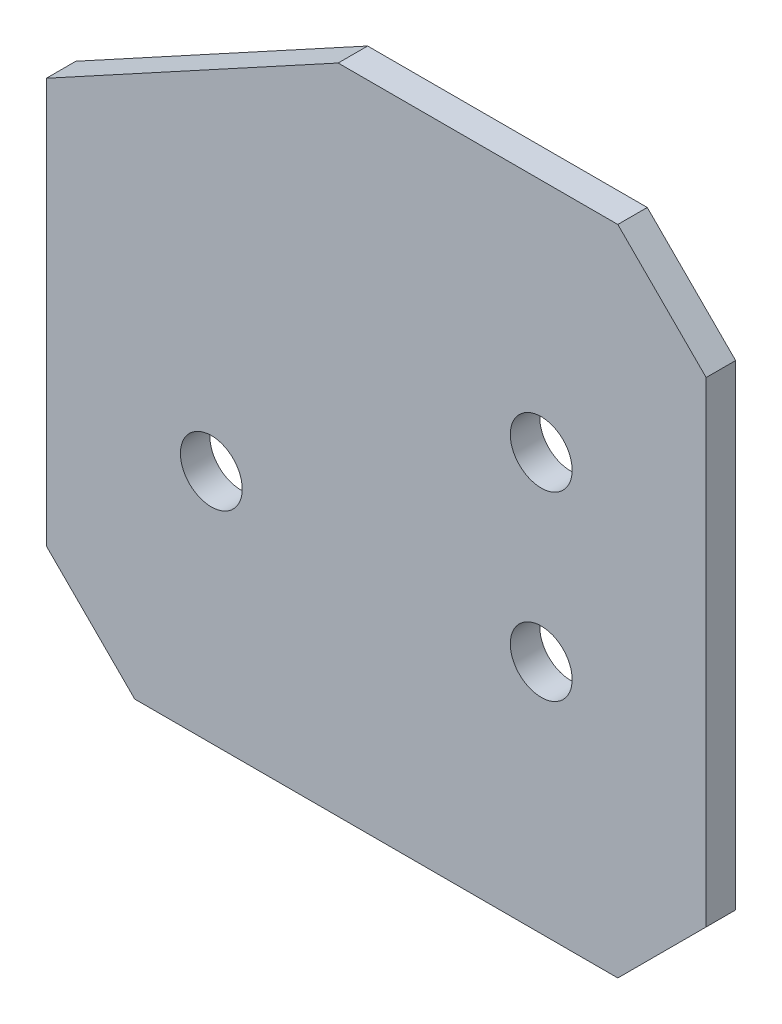
SolidWorks part; units mm, degrees
note: The reader was unsure of these and kept them because the rebuilt part matched: thickness of "Базовая кромка1", "Листовой металл3", "Листовой металл4".
material "AISI 1020"
ref_plane "Спереди" through (0, 0, 0) normal (0, 0, 1) x (1, 0, 0)
ref_plane "Сверху" through (0, 0, 0) normal (0, 1, 0) x (1, 0, 0)
ref_plane "Справа" through (0, 0, 0) normal (1, 0, 0) x (0, 0, -1)
sketch "Эскиз1" plane through (0, 0, 0) normal (0, 0, 1) x (1, 0, 0)
  line L0 (0, -1000) -> (0, 49000) construction
  line L1 (56, 3) -> (-56, 3)
  line L2 (-530.3264, 86.7738) -> (144.1634, 86.7738) construction
  line L3 (-56, 3) -> (-56, 113.7738)
  line L5 (-537.2086, 113.7738) -> (144.1634, 113.7738) construction
  line L6 (-56, 113.7738) -> (56, 113.7738)
  line L7 (133.9446, 3) -> (-133.9446, 3) construction
  line L8 (133.9446, 3) -> (-133.9446, 3) construction
  line L9 (-15, 30) -> (-15, 86.7738) construction
  line L10 (164.1634, 30) -> (-740.8168, 30) construction
  line L11 (0, 73.7738) -> (-56, 73.7738) construction
  line L12 (56, 3) -> (56, 113.7738)
  circle A0 centre (-28, 73.7738) radius 5.25 construction
  circle A1 centre (-28, 73.7738) radius 13 construction
  circle A2 centre (-28, 43) radius 5.25
  circle A3 centre (-28, 43) radius 13 construction
  circle A4 centre (28, 73.7738) radius 5.25
  circle A5 centre (28, 43) radius 5.25
  point P27 (-28, 73.7738)
  point P33 (0, 3)
  point P34 (0, 113.7738)
  dimension "D1" = 10.5
  dimension "D2" = 26
base flange "Базовая кромка1" sketch "Эскиз1" thickness 5 reverse thickness direction no parameters "D1"=0.74
chamfer "Фаска1" distance 15 angle 45 4 edges at (56, 3, -2.5) (-56, 3, -2.5) (56, 113.7738, -2.5) (-56, 113.7738, -2.5)
sketch "Эскиз2" plane through (0, 0, 0) normal (0, 0, 1) x (1, 0, 0)
  line L0 (-56, 113.7738) -> (-56, 86.7684)
  line L1 (-56, 3) -> (-56, 113.7738) construction
  line L2 (-56, 86.7684) -> (-6.4685, 113.7738)
  line L3 (-56, 113.7738) -> (56, 113.7738) construction
  line L4 (-6.4685, 113.7738) -> (-56, 113.7738)
  line L5 (-6.4685, 113.7738) -> (-160.121, 30) construction
extrude "Вырез-Вытянуть1" cut sketch "Эскиз2" against normal blind 10
sketch "Сгиб-Линии1" [suppressed] plane through (0, 0, 0) normal (0, 1, 0) x (1, 0, 0)
sketch "Граничная рамка1" [suppressed] plane through (0, 0, 0) normal (0, 1, 0) x (1, 0, 0)
sheet metal parameters "Листовой металл3" thickness 5 parameters "D1"=0.74, "D7"=4
flat pattern "Развертка3" [suppressed]
sketch "Сгиб-Линии2" plane through (0, 0, 0) normal (0, 1, 0) x (1, 0, 0)
sketch "Граничная рамка2" [suppressed] plane through (0, 0, 0) normal (0, 1, 0) x (1, 0, 0)
sheet metal parameters "Листовой металл4" thickness 5 parameters "D1"=0.74, "D7"=4
flat pattern "Развертка3"
sketch "Сгиб-Линии2" plane through (0, 0, 0) normal (0, 1, 0) x (1, 0, 0)
sketch3d "Граничная рамка2" [suppressed]
  line L0 (-56, 3, 0) -> (56, 3, 0) construction
  line L1 (-56, 113.7738, 0) -> (56, 113.7738, 0) construction
  line L2 (-56, 3, 0) -> (-56, 113.7738, 0) construction
  line L3 (56, 3, 0) -> (56, 113.7738, 0) construction
